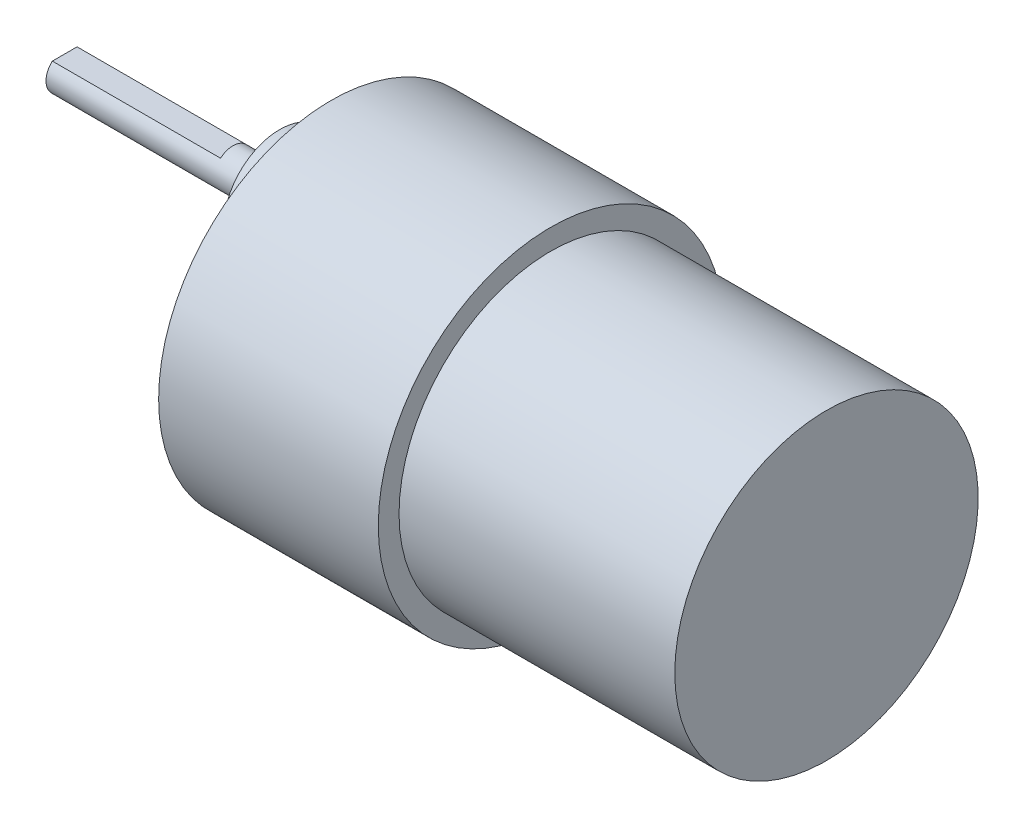
SolidWorks part; units mm, degrees
ref_plane "Front Plane" through (0, 0, 0) normal (0, 0, 1) x (1, 0, 0)
ref_plane "Top Plane" through (0, 0, 0) normal (0, 1, 0) x (1, 0, 0)
ref_plane "Right Plane" through (0, 0, 0) normal (1, 0, 0) x (0, 0, -1)
sketch "Sketch1" plane through (0, 0, 0) normal (0, 0, 1) x (1, 0, 0)
  line L1 (0, 0) -> (23.5, 0)
  line L2 (0, 0) -> (0, 18.45)
  line L3 (0, 18.45) -> (23.5, 18.45)
  line L4 (23.5, 0) -> (23.5, 18.45)
  line L5 (23.5, 16.23) -> (53, 16.23)
  line L6 (23.5, 16.23) -> (23.5, 0)
  line L7 (23.5, 0) -> (53, 0)
  line L8 (53, 16.23) -> (53, 0)
  dimension "D1" = 23.5
  dimension "D2" = 29.5
  dimension "D3" = 16.23
  dimension "D4" = 18.45
revolve "Revolve1" add sketch "Sketch1" angle 360 about L1 region at (11.75, 9.225, 0) region at (38.25, 8.115, 0)
sketch "Sketch2" plane through (0, 0, 0) normal (-1, 0, 0) x (0, 0, 1)
  line L0 (0, 0) -> (0, 18.45) construction
  line L1 (0, 0) -> (7.75, 13.4234) construction
  circle A0 centre (0, 0) radius 15.5 construction
  circle A1 centre (0, 0) radius 18.45 construction
  point P1 (7.75, 13.4234)
  point P4 (15.5, 0)
  point P7 (7.75, -13.4234)
  point P8 (-7.75, -13.4234)
  point P9 (-15.5, 0)
  point P10 (-7.75, 13.4234)
  point P11 (0, 0)
  dimension "D1" = 31
  dimension "D3" = 30
  dimension "D2" = 6
hole_wizard "M3.5x0.6 Tapped Hole1" positions "Sketch3" profile "Sketch5" tap size "M3.5x0.6" standard "ANSI Metric"
sketch "Sketch3" plane through (0, 0, 0) normal (-1, 0, 0) x (0, 0, 1)
  point P0 (7.75, 13.4234)
  point P3 (15.5, 0)
  point P6 (7.75, -13.4234)
  point P9 (-7.75, -13.4234)
  point P12 (-15.5, 0)
  point P15 (-7.75, 13.4234)
sketch "Sketch5" plane through (0, 13.4234, 7.75) normal (0, 1, 0) x (0, 0, 1)
  line L0 (0, 0) -> (0, 4.3712)
  line L1 (0, 4.3712) -> (1.45, 3.5)
  line L2 (1.45, 3.5) -> (1.45, 0)
  line L5 (1.45, 0) -> (0, 0)
  line L10 (0, 4.3712) -> (-1.45, 3.5) construction
  line L11 (0, -6.35) -> (0, 107.95) construction
  dimension "Tap Drill Dia." = 2.9
  dimension "Tap Drill Depth" = 3.5
  dimension "Drill Angle" = 118
cosmetic thread "Hole Thread1" parameters "D1"=7, "D2"=3.5
cosmetic thread "Hole Thread2" parameters "D1"=7, "D2"=3.5
cosmetic thread "Hole Thread3" parameters "D1"=7, "D2"=3.5
cosmetic thread "Hole Thread4" parameters "D1"=7, "D2"=3.5
cosmetic thread "Hole Thread5" parameters "D1"=7, "D2"=3.5
cosmetic thread "Hole Thread6" parameters "D1"=7, "D2"=3.5
sketch "Sketch6" plane through (0, 0, 0) normal (-1, 0, 0) x (0, 0, 1)
  circle A0 centre (0, 7) radius 6
  dimension "D2" = 12
  dimension "D1" = 7
extrude "Boss-Extrude1" add sketch "Sketch6" along normal blind 5.5
sketch "Sketch7" plane through (-5.5, 0, 0) normal (-1, 0, 0) x (0, 0, 1)
  circle A0 centre (0, 7) radius 2
  dimension "D1" = 4
extrude "Boss-Extrude2" add sketch "Sketch7" along normal blind 23
sketch "Sketch8" plane through (-28.5, 0, 0) normal (-1, 0, 0) x (0, 0, 1)
  line L0 (-1.3229, 8.5) -> (1.3229, 8.5)
  circle A0 centre (0, 7) radius 2 construction
  circle A1 centre (0, 7) radius 2
  circle M2 centre (0, 7) radius 2
  dimension "D1" = 3.5
extrude "Cut-Extrude1" cut sketch "Sketch8" against normal blind 18 contours L0 M2 region at (-28.5, 8.7023, 0)
